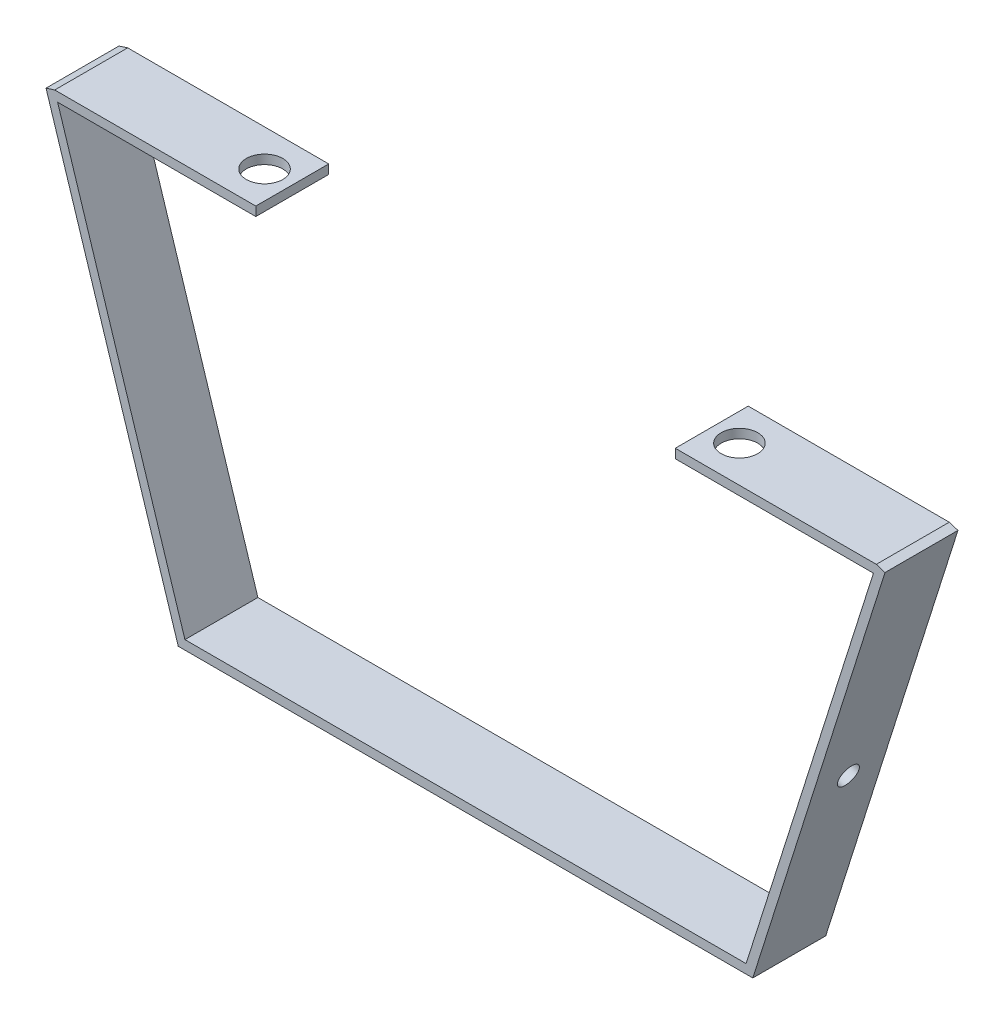
SolidWorks part; units mm, degrees
ref_plane "Front Plane" through (0, 0, 0) normal (0, 0, 1) x (1, 0, 0)
ref_plane "Top Plane" through (0, 0, 0) normal (0, 1, 0) x (1, 0, 0)
ref_plane "Right Plane" through (0, 0, 0) normal (1, 0, 0) x (0, 0, -1)
sketch "Sketch1" plane through (0, 0, 0) normal (0, 0, 1) x (1, 0, 0)
  line L0 (-95.9147, -24.4509) -> (104.1103, -24.4509)
  line L1 (104.1103, -24.4509) -> (150.1478, 120.8292)
  line L2 (-95.9147, -24.4509) -> (-141.9522, 120.8292)
  line L3 (101.7858, -21.2759) -> (147.1211, 121.7883)
  line L4 (-93.5902, -21.2759) -> (101.7858, -21.2759)
  line L5 (-93.5902, -21.2759) -> (-138.9256, 121.7883)
  line L6 (-141.9522, 120.8292) -> (-138.9256, 121.7883)
  line L7 (147.1211, 121.7883) -> (150.1478, 120.8292)
  dimension "D1" = 152.4
  dimension "D2" = 152.4
  dimension "D3" = 200.025
  dimension "D4" = 292.1
  dimension "D5" = 3.175
extrude "Boss-Extrude1" add sketch "Sketch1" along normal blind 25.4
sketch "Sketch4" plane through (0, 0, 0) normal (0, 0, -1) x (-1, 0, 0)
  line L0 (-147.1211, 121.7883) -> (138.9256, 121.7883)
  line L2 (-146.115, 118.6133) -> (137.9194, 118.6133)
  line L4 (-147.1211, 121.7883) -> (-101.7858, -21.2759) construction
  line L6 (141.9522, 120.8292) -> (138.9256, 121.7883)
  line L7 (-147.1211, 121.7883) -> (-150.1478, 120.8292)
  line L8 (93.5902, -21.2759) -> (138.9256, 121.7883) construction
  line L9 (-146.115, 118.6133) -> (-150.1478, 120.8292)
  line L10 (137.9194, 118.6133) -> (141.9522, 120.8292)
  line L12 (-77.1211, 121.7883) -> (68.9256, 121.7883)
  line L13 (-77.1211, 121.7883) -> (-77.1211, 118.6133)
  line L14 (-77.1211, 118.6133) -> (68.9256, 118.6133)
  line L15 (68.9256, 121.7883) -> (68.9256, 118.6133)
  line M6 (138.9256, 121.7883) -> (93.5902, -21.2759)
  line M8 (-101.7858, -21.2759) -> (-147.1211, 121.7883)
  dimension "D1" = 3.175
  dimension "D2" = 70
  dimension "D3" = 70
extrude "Boss-Extrude2" add sketch "Sketch4" against normal blind 25.4 contours L13 L0 L2 M8 | L0 L15 L2 M6 region at (111.8702, 120.2046, 0) region at (-103.6746, 120.2046, 0)
sketch "Sketch6" plane through (0, 121.7883, 0) normal (0, 1, 0) x (1, 0, 0)
  line L1 (-138.9256, -25.4) -> (-138.9256, 0) construction
  line L2 (147.1211, -25.4) -> (147.1211, 0) construction
  line L3 (147.1211, 0) -> (77.1211, 0) construction
  circle A0 centre (-78.5756, -12.7) radius 6.35
  circle A1 centre (86.7711, -12.7) radius 6.35
  dimension "D1" = 12.7
  dimension "D2" = 12.7
  dimension "D3" = 60.35
  dimension "D4" = 60.35
extrude "Cut-Extrude1" cut sketch "Sketch6" against normal blind 10
sketch "Sketch7" plane through (101.6509, -32.2119, 0) normal (0.9533, -0.3021, 0) x (0, 0, -1)
  line L0 (0, 8.1414) -> (0, 160.5414) construction
  circle A0 centre (-12.7, 76.2859) radius 3.675
  dimension "D2" = 7.35
  dimension "D1" = 12.7
extrude "Cut-Extrude2" cut sketch "Sketch7" against normal blind 3.175
